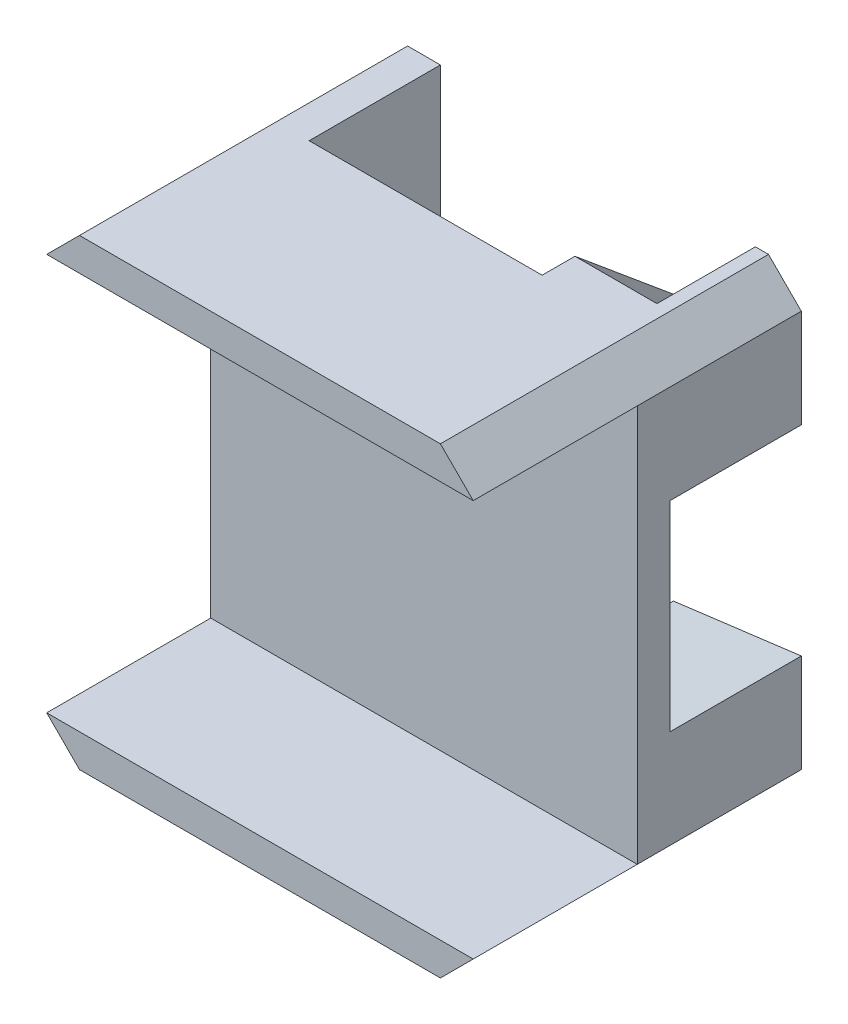
SolidWorks part; units mm, degrees
ref_plane "Front Plane" through (0, 0, 0) normal (0, 0, 1) x (1, 0, 0)
ref_plane "Top Plane" through (0, 0, 0) normal (0, 1, 0) x (1, 0, 0)
ref_plane "Right Plane" through (0, 0, 0) normal (1, 0, 0) x (0, 0, -1)
sketch "Sketch1" plane through (0, 0, 0) normal (0, 0, 1) x (1, 0, 0)
  line L1 (-6.5, -7.05) -> (6.5, -7.05)
  line L2 (-6.5, -7.05) -> (-6.5, 7.05)
  line L3 (-6.5, 7.05) -> (6.5, 7.05)
  line L4 (6.5, -7.05) -> (6.5, 7.05)
  line L5 (-6.5, -7.05) -> (6.5, 7.05) construction
  line L6 (-6.5, 7.05) -> (6.5, -7.05) construction
  line L7 (-6.5, -6.05) -> (6.5, -6.05)
  line L8 (-6.5, -6.05) -> (-6.5, 6.05)
  line L9 (-6.5, 6.05) -> (6.5, 6.05)
  line L10 (6.5, -6.05) -> (6.5, 6.05)
  line L11 (-6.5, -6.05) -> (6.5, 6.05) construction
  line L12 (-6.5, 6.05) -> (6.5, -6.05) construction
  point P0 (0, 0)
  point P6 (0, 0)
  dimension "D1" = 12.1
  dimension "D2" = 1
  dimension "D3" = 13
extrude "Boss-Extrude1" add sketch "Sketch1" along normal blind 6 contours L2 L9 L4 L3 | L7 L2 L1 L4 region at (0, -6.55, 0) region at (0, 6.55, 0)
extrude "Boss-Extrude2" add sketch "Sketch1<3>" along normal blind 1 contours L9 L2 L7 L4 region at (0, 0, 0)
sketch "Sketch1<3>" plane through (0, 0, 0) normal (0, 0, 1) x (1, 0, 0) same geometry as "Sketch1"
sketch "Sketch2" plane through (0, 0, 0) normal (0, 0, -1) x (-1, 0, 0)
  line L1 (6.5, -7.05) -> (-6.5, -7.05) construction
  line L2 (6.5, 7.05) -> (4.5, 7.05)
  line L3 (6.5, 7.05) -> (6.5, -7.05)
  line L4 (6.5, -7.05) -> (4.5, -7.05)
  line L5 (4.5, 7.05) -> (4.5, -7.05)
  line L6 (-6.5, -3.05) -> (-2.6, -3.55)
  line L8 (-6.5, -7.05) -> (-6.5, 7.05) construction
  line L9 (-2.6, -3.55) -> (-2.6, -7.05)
  line L10 (-2.6, -7.05) -> (-6.5, -7.05)
  line L11 (-6.5, -7.05) -> (-6.5, -3.05)
  line L13 (-6.5, 7.05) -> (-2.6, 7.05)
  line L14 (6.5, 7.05) -> (-6.5, 7.05) construction
  line L15 (-2.6, 7.05) -> (-2.6, 3.55)
  line L16 (-2.6, 3.55) -> (-6.5, 3.05)
  line L17 (-6.5, 3.05) -> (-6.5, 7.05)
  dimension "D1" = 2
  dimension "D2" = 7.1
  dimension "D3" = 7.1
  dimension "D4" = 7.1
  dimension "D5" = 3.5
  dimension "D6" = 6.1
  dimension "D7" = 4
extrude "Boss-Extrude3" add sketch "Sketch2" along normal blind 4
chamfer "Chamfer1" distance 1 angle 45 4 edges at (-6.5, -7.05, 1) (6.5, -7.05, 1) (-6.5, 7.05, 1) (6.5, 7.05, 1)
sketch "Sketch3" plane through (2.6, 0, 0) normal (-1, 0, 0) x (0, 0, 1)
  line L0 (-1, -7.05) -> (-4, -4.55)
  line L1 (6, -7.05) -> (-4, -7.05) construction
  line L2 (-4, -6.05) -> (-4, 6.05) construction
  line L3 (-4, -4.55) -> (-4, -7.05)
  line L4 (-4, -7.05) -> (-4, -6.05) construction
  line L5 (-4, -7.05) -> (-1, -7.05)
  line L6 (-1, 7.05) -> (-4, 4.55)
  line L7 (-4, 7.05) -> (6, 7.05) construction
  line L8 (-4, 4.55) -> (-4, 7.05)
  line L9 (-4, 7.05) -> (-1, 7.05)
  dimension "D1" = 2.5
  dimension "D2" = 3
  dimension "D3" = 2.5
  dimension "D4" = 3
extrude "Cut-Extrude1" cut sketch "Sketch3" against normal blind 2.5
